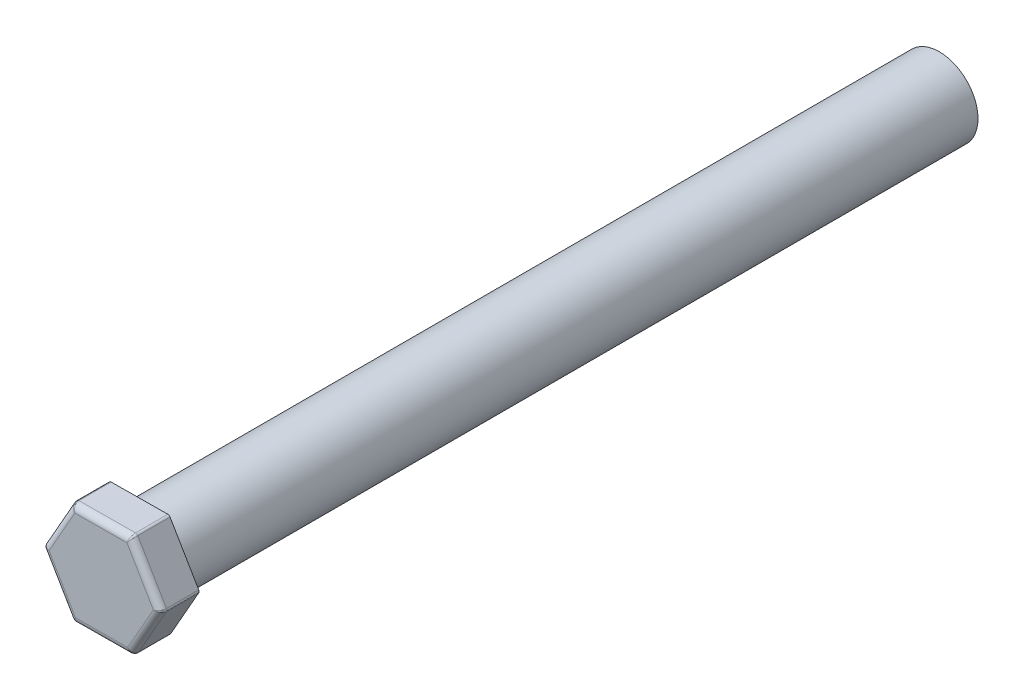
SolidWorks part; units mm, degrees
ref_plane "Front Plane" through (0, 0, 0) normal (0, 0, 1) x (1, 0, 0)
ref_plane "Top Plane" through (0, 0, 0) normal (0, 1, 0) x (1, 0, 0)
ref_plane "Right Plane" through (0, 0, 0) normal (1, 0, 0) x (0, 0, -1)
sketch "Sketch1" plane through (0, 0, 0) normal (0, 0, 1) x (1, 0, 0)
  circle A0 centre (-432, 0) radius 30
extrude "Boss-Extrude1" add sketch "Sketch1" against normal blind 620 contours A0
sketch "Sketch2" plane through (0, 0, 0) normal (0, 0, 1) x (1, 0, 0)
  line L1 (-408.0386, -38.8225) -> (-386.3831, -0.66)
  line L2 (-386.398, 1.3399) -> (-408.62, 39.1754)
  line L3 (-410.3594, 40.1624) -> (-454.2369, 39.8354)
  line L4 (-455.9614, 38.8225) -> (-477.6169, 0.66)
  line L5 (-477.602, -1.3399) -> (-455.38, -39.1754)
  line L6 (-453.6406, -40.1624) -> (-409.7631, -39.8354)
  circle A0 centre (-432, 0) radius 40 construction
  arc A1 (-455.38, -39.1754) -> (-453.6406, -40.1624) centre (-453.6555, -38.1625) ccw
  arc A2 (-477.6169, 0.66) -> (-477.602, -1.3399) centre (-475.8774, -0.3271) ccw
  arc A3 (-454.2369, 39.8354) -> (-455.9614, 38.8225) centre (-454.2219, 37.8354) ccw
  arc A4 (-408.62, 39.1754) -> (-410.3594, 40.1624) centre (-410.3445, 38.1625) ccw
  arc A5 (-386.3831, -0.66) -> (-386.398, 1.3399) centre (-388.1226, 0.3271) ccw
  arc A6 (-408.0386, -38.8225) -> (-409.7631, -39.8354) centre (-409.7781, -37.8354) cw
  dimension "D1" = 80
  dimension "D2" = 2
extrude "Boss-Extrude2" add sketch "Sketch2" along normal blind 30
fillet "Fillet1" radius 5 12 edges at (-409.3575, 39.9019, 30) (-397.509, 20.2576, 30) (-386.1227, 0.342, 30) (-397.2109, -19.7412, 30) (-408.7652, -39.56, 30) (-431.7019, -39.9989, 30) (-454.6425, -39.9019, 30) (-466.491, -20.2576, 30) (-477.8773, -0.342, 30) (-466.7891, 19.7412, 30) (-455.2348, 39.56, 30) (-432.2981, 39.9989, 30)
